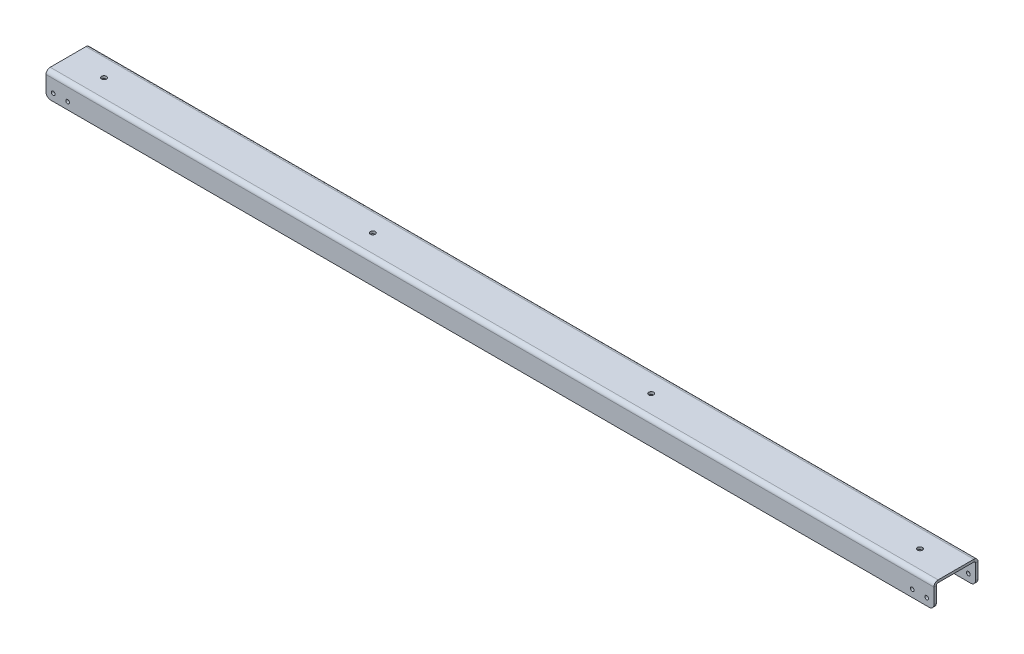
SolidWorks part; units mm, degrees
note: The reader was unsure of these and kept them because the rebuilt part matched: flange length of "Edge-Flange1".
material "6061 Alloy"
ref_plane "Front Plane" through (0, 0, 0) normal (0, 0, 1) x (1, 0, 0)
ref_plane "Top Plane" through (0, 0, 0) normal (0, 1, 0) x (1, 0, 0)
ref_plane "Right Plane" through (0, 0, 0) normal (1, 0, 0) x (0, 0, -1)
sketch "Sketch1" plane through (0, 0, 0) normal (0, 1, 0) x (1, 0, 0)
  line L1 (-587.375, -25.908) -> (587.375, -25.908)
  line L2 (-587.375, -25.908) -> (-587.375, 25.908)
  line L3 (-587.375, 25.908) -> (587.375, 25.908)
  line L4 (587.375, -25.908) -> (587.375, 25.908)
  line L5 (-587.375, -25.908) -> (587.375, 25.908) construction
  line L6 (-587.375, 25.908) -> (587.375, -25.908) construction
  point P0 (0, 0)
  dimension "D1" = 1174.75
  dimension "D2" = 51.816
base flange "Base-Flange1" sketch "Sketch1" thickness 3.2639 reverse thickness direction no parameters "D1"=2.286
edge flange "Edge-Flange1" sketch "Sketch10" flange profiles "Sketch10", "Sketch11" flange angle 90 flange length 28.575 flange position material outside bend radius 2.286 thickness 3.2639 relief rectangular parameters "D1"=3.302, "D6"=10, "D8"=1
sketch "Sketch10" plane through (0, -3.2639, 25.908) normal (0, 0, -1) x (1, 0, 0)
  line L2 (-587.375, 0) -> (-587.375, 28.575)
  line L3 (-587.375, 28.575) -> (587.375, 28.575)
  line L4 (587.375, 28.575) -> (587.375, 0)
  line L9 (587.375, 0) -> (-587.375, 0) construction
  line L10 (587.375, 0) -> (-587.375, 0)
  dimension "D1" = 28.575
sketch "Sketch11" plane through (0, -3.2639, -25.908) normal (0, 0, 1) x (-1, 0, 0)
  line L2 (-587.375, 0) -> (-587.375, 28.575)
  line L3 (-587.375, 28.575) -> (587.375, 28.575)
  line L4 (587.375, 28.575) -> (587.375, 0)
  line L13 (587.375, 0) -> (-587.375, 0) construction
  line L14 (587.375, 0) -> (-587.375, 0)
bend "EdgeBend1" bend radius 2.286 bend angle 90 parameters "D5"=1
bend "EdgeBend2" bend radius 2.286 bend angle 90 parameters "D5"=2
sketch "Sketch12" plane through (0, 0, 29.1719) normal (0, 0, 1) x (1, 0, 0)
  line L0 (587.375, -31.8389) -> (-587.375, -31.8389) construction
  line L1 (555.625, -31.8389) -> (-555.625, -31.8389)
  line L2 (555.625, -31.8389) -> (555.625, 1.4986)
  line L3 (555.625, 1.4986) -> (-555.625, 1.4986)
  line L4 (-555.625, -31.8389) -> (-555.625, 1.4986)
  line L5 (0, 1.4986) -> (0, -31.8389) construction
  line L6 (555.625, -15.1702) -> (-555.625, -15.1702) construction
  line L7 (-587.375, -31.8389) -> (-587.375, -5.5499) construction
  line L8 (587.375, -5.5499) -> (587.375, -31.8389) construction
  point P68 (0, -15.1702)
  dimension "D1" = 31.75
  dimension "D2" = 31.75
  dimension "D3" = 33.3375
extrude "Cut-Extrude1" [suppressed] cut sketch "Sketch12" against normal through all both and the other way through all
hole_wizard "#10 (0.1935) Diameter Hole1" [suppressed] positions "Sketch13" profile "Sketch14" hole size "#10" standard "ANSI Inch"
sketch "Sketch13" [suppressed] plane through (0, 0, 24.5187) normal (0, 0, 1) x (1, 0, 0)
  line L0 (-571.5, -30.075) -> (-571.5, -3) construction
  line L1 (-555.625, -30.075) -> (-587.375, -30.075) construction
  line L2 (587.375, -3) -> (555.625, -3) construction
  line L4 (-555.625, -22.1375) -> (-587.375, -22.1375) construction
  line L5 (-587.375, -30.075) -> (-587.375, -3) construction
  line L7 (-587.375, -22.1375) -> (-587.375, -30.075) construction
  line L9 (-587.375, -26.1063) -> (-577.85, -39.6) construction
  line L11 (-571.5, -30.075) -> (-587.375, -30.075) construction
  line L13 (-579.4375, -30.075) -> (-579.4375, -22.1375) construction
  line L15 (571.5, -30.075) -> (571.5, -3) construction
  line L16 (587.375, -30.075) -> (555.625, -30.075) construction
  line L18 (577.85, -39.6) -> (587.375, -39.6) construction
  line L20 (587.375, -3) -> (587.375, -30.075) construction
  line L22 (571.5, -30.075) -> (587.375, -30.075) construction
  line L24 (579.4375, -30.075) -> (579.4375, -3) construction
  point P0 (563.5625, -20.55)
  point P2 (579.4375, -20.55)
  point P4 (-579.4375, -20.55)
  point P6 (-563.5625, -20.55)
  dimension "D1" = 9.525
  dimension "D2" = 9.525
  dimension "D3" = 7.9375
  dimension "D5" = 9.525
  dimension "D6" = 7.9375
sketch "Sketch14" plane through (563.5625, -20.55, 24.5187) normal (1, 0, 0) x (0, -1, 0)
  line L0 (0, 0) -> (0, 49.0375)
  line L1 (0, 49.0375) -> (2.4574, 49.0375)
  line L2 (2.4574, 49.0375) -> (2.4574, 0)
  line L5 (2.4574, 0) -> (0, 0)
  line L11 (0, -6.35) -> (0, 107.95) construction
  dimension "Thru Hole Dia." = 4.9149
  dimension "Thru Hole Depth" = 49.0375
hole_wizard "#10 (0.1935) Diameter Hole2" positions "Sketch19" profile "Sketch20" hole size "#10" standard "ANSI Inch" end condition through all
sketch "Sketch19" plane through (0, 0, 29.1719) normal (0, 0, 1) x (1, 0, 0)
  line L0 (587.375, -5.5499) -> (587.375, -31.8389) construction
  line L1 (587.375, -31.8389) -> (-587.375, -31.8389) construction
  line L2 (0, -31.8389) -> (0, -5.5499) construction
  line L3 (587.375, -5.5499) -> (-587.375, -5.5499) construction
  point P0 (577.85, -22.3139)
  point P2 (558.8, -22.3139)
  point P16 (-558.8, -22.3139)
  point P17 (-577.85, -22.3139)
  dimension "D1" = 9.525
  dimension "D2" = 19.05
  dimension "D3" = 9.525
sketch "Sketch20" plane through (577.85, -22.3139, 29.1719) normal (1, 0, 0) x (0, -1, 0)
  line L0 (0, 0) -> (0, 58.3438)
  line L1 (0, 58.3438) -> (2.4574, 58.3438)
  line L2 (2.4574, 58.3438) -> (2.4574, 0)
  line L5 (2.4574, 0) -> (0, 0)
  line L11 (0, -6.35) -> (0, 107.95) construction
  dimension "Thru Hole Dia." = 4.9149
  dimension "Thru Hole Depth" = 58.3438
fillet "Fillet2" radius 6.35 4 edges at (-587.375, -31.8389, 27.54) (-587.375, -31.8389, -27.54) (587.375, -31.8389, 27.54) (587.375, -31.8389, -27.54)
hole_wizard "1/4 Clearance Hole1" positions "Sketch23" profile "Sketch22" hole size "1/4" standard "ANSI Inch" end condition through all
sketch "Sketch23" plane through (0, 0, 0) normal (0, 1, 0) x (1, 0, 0)
  line L0 (-587.375, 23.622) -> (-587.375, -23.622) construction
  line L2 (-587.375, 0) -> (587.375, 0) construction
  line L3 (587.375, -23.622) -> (587.375, 23.622) construction
  line L4 (0, -23.622) -> (0, 23.622) construction
  line L5 (-587.375, -23.622) -> (587.375, -23.622) construction
  line L6 (587.375, 23.622) -> (-587.375, 23.622) construction
  point P0 (539.75, 0)
  point P2 (184.15, 0)
  point P6 (-184.15, 0)
  point P8 (-539.75, 0)
  dimension "D1" = 47.625
  dimension "D2" = 47.625
  dimension "D3" = 355.6
sketch "Sketch22" plane through (539.75, 0, 0) normal (1, 0, 0) x (0, 0, 1)
  line L0 (0, 0) -> (0, 31.8389)
  line L1 (0, 31.8389) -> (3.2639, 31.8389)
  line L2 (3.2639, 31.8389) -> (3.2639, 0)
  line L5 (3.2639, 0) -> (0, 0)
  line L11 (0, -6.35) -> (0, 107.95) construction
  dimension "Thru Hole Dia." = 6.5278
  dimension "Thru Hole Depth" = 31.8389
sketch "Bend-Lines1" [suppressed] plane through (0, 0, 0) normal (0, 1, 0) x (1, 0, 0)
sketch "Bounding-Box1" [suppressed] plane through (0, 0, 0) normal (0, 1, 0) x (1, 0, 0)
sheet metal parameters "Sheet-Metal1" thickness 3.2639 parameters "D1"=1.5
flat pattern "Flat-Pattern1" [suppressed]
sketch "Bend-Lines2" plane through (0, 0, 0) normal (0, 1, 0) x (1, 0, 0)
sketch3d "Bounding-Box2" [suppressed]
  line L0 (-609.6, 23.0188, 0) -> (609.6, 23.0188, 0) construction
  line L1 (-609.6, -23.0187, 0) -> (609.6, -23.0187, 0) construction
  line L2 (-609.6, 23.0188, 0) -> (-609.6, -23.0187, 0) construction
  line L3 (609.6, 23.0188, 0) -> (609.6, -23.0187, 0) construction
sheet metal parameters "Sheet-Metal2" thickness 3.2639 parameters "D1"=1.5
flat pattern "Flat-Pattern1"
sketch "Bend-Lines2" plane through (0, 0, 0) normal (0, 1, 0) x (1, 0, 0)
  line L0 (587.375, 24.3388) -> (-587.375, 24.3388) construction
  line L1 (-587.375, -24.3388) -> (587.375, -24.3388) construction
  line L2 (587.375, 24.3388) -> (-587.375, 24.3388) construction
  line L3 (-587.375, -24.3388) -> (587.375, -24.3388) construction
sketch3d "Bounding-Box2" [suppressed]
  line L0 (587.375, 52.6464, 0) -> (-587.375, 52.6464, 0) construction
  line L1 (587.375, -52.6464, 0) -> (-587.375, -52.6464, 0) construction
  line L2 (587.375, 52.6464, 0) -> (587.375, -52.6464, 0) construction
  line L3 (-587.375, 52.6464, 0) -> (-587.375, -52.6464, 0) construction
bend of the flat pattern "Flatten-<EdgeBend1>1"
bend of the flat pattern "Flatten-<EdgeBend2>1"
sheet metal parameters "Sheet-Metal3" thickness 3.2639 parameters "D1"=1.5
flat pattern "Flat-Pattern1"
sketch "Bend-Lines2" plane through (0, 0, 0) normal (0, 1, 0) x (1, 0, 0)
  line L0 (609.6, 23.2859) -> (-609.6, 23.2859) construction
  line L1 (-609.6, -23.2859) -> (609.6, -23.2859) construction
  line L2 (609.6, 23.2859) -> (-609.6, 23.2859) construction
  line L3 (-609.6, -23.2859) -> (609.6, -23.2859) construction
sketch3d "Bounding-Box2" [suppressed]
  line L0 (609.6, 68.003, 0) -> (-609.6, 68.003, 0) construction
  line L1 (609.6, -68.003, 0) -> (-609.6, -68.003, 0) construction
  line L2 (609.6, 68.003, 0) -> (609.6, -68.003, 0) construction
  line L3 (-609.6, 68.003, 0) -> (-609.6, -68.003, 0) construction
bend of the flat pattern "Flatten-<EdgeBend1>1"
bend of the flat pattern "Flatten-<EdgeBend2>1"
sheet metal parameters "Sheet-Metal4" thickness 3.2639 parameters "D1"=1.5
flat pattern "Flat-Pattern5"
sketch "Bend-Lines3" plane through (0, 0, 0) normal (0, 1, 0) x (1, 0, 0)
  line L0 (-555.625, 23.2859) -> (-587.375, 23.2859) construction
  line L1 (-587.375, -23.2859) -> (-555.625, -23.2859) construction
  line L2 (-555.625, 23.2859) -> (-587.375, 23.2859) construction
  line L3 (-587.375, -23.2859) -> (-555.625, -23.2859) construction
sketch3d "Bounding-Box3" [suppressed]
  line L0 (-587.375, -52.128, 0) -> (-587.375, 52.128, 0) construction
  line L1 (-555.625, -52.128, 0) -> (-555.625, 52.128, 0) construction
  line L2 (-587.375, -52.128, 0) -> (-555.625, -52.128, 0) construction
  line L3 (-587.375, 52.128, 0) -> (-555.625, 52.128, 0) construction
bend of the flat pattern "Flatten-<EdgeBend1>1"
bend of the flat pattern "Flatten-<EdgeBend2>1"
sheet metal parameters "Sheet-Metal5" thickness 3.2639 parameters "D1"=1.5
flat pattern "Flat-Pattern5" [suppressed]
sketch "Bend-Lines3" plane through (0, 0, 0) normal (0, 1, 0) x (1, 0, 0)
sketch "Bounding-Box3" [suppressed] plane through (0, 0, 0) normal (0, 1, 0) x (1, 0, 0)
bend of the flat pattern "Flatten-<EdgeBend2>2"
bend of the flat pattern "Flatten-<EdgeBend1>2"
sheet metal parameters "Sheet-Metal6" thickness 3.2639 parameters "D1"=1.5
flat pattern "Flat-Pattern6" [suppressed]
sketch "Bend-Lines4" plane through (0, 0, 0) normal (0, 1, 0) x (1, 0, 0)
sketch "Bounding-Box4" [suppressed] plane through (0, 0, 0) normal (0, 1, 0) x (1, 0, 0)
bend of the flat pattern "Flatten-<EdgeBend2>3"
bend of the flat pattern "Flatten-<EdgeBend1>3"
sheet metal parameters "Sheet-Metal7" thickness 3.2639 parameters "D1"=1.5
flat pattern "Flat-Pattern6" [suppressed]
sketch "Bend-Lines4" plane through (0, 0, 0) normal (0, 1, 0) x (1, 0, 0)
sketch "Bounding-Box4" [suppressed] plane through (0, 0, 0) normal (0, 1, 0) x (1, 0, 0)
bend of the flat pattern "Flatten-<EdgeBend2>3"
bend of the flat pattern "Flatten-<EdgeBend1>3"
sheet metal parameters "Sheet-Metal8" thickness 3.2639 parameters "D1"=1.5
flat pattern "Flat-Pattern1"
sketch "Bend-Lines2" plane through (0, 0, 0) normal (0, 1, 0) x (1, 0, 0)
  line L0 (587.375, 24.3388) -> (-587.375, 24.3388) construction
  line L1 (-587.375, -24.3388) -> (587.375, -24.3388) construction
  line L2 (587.375, 24.3388) -> (-587.375, 24.3388) construction
  line L3 (-587.375, -24.3388) -> (587.375, -24.3388) construction
sketch3d "Bounding-Box2" [suppressed]
  line L0 (-587.375, 52.6461, 0) -> (587.375, 52.6464, 0) construction
  line L1 (-587.375, -52.6464, 0) -> (587.375, -52.6461, 0) construction
  line L2 (-587.375, 52.6461, 0) -> (-587.375, -52.6464, 0) construction
  line L3 (587.375, 52.6464, 0) -> (587.375, -52.6461, 0) construction
bend of the flat pattern "Flatten-<EdgeBend1>1"
bend of the flat pattern "Flatten-<EdgeBend2>1"
sheet metal parameters "Sheet-Metal9" thickness 3.2639 parameters "D1"=1.5
flat pattern "Flat-Pattern1"
sketch "Bend-Lines2" plane through (0, 0, 0) normal (0, 1, 0) x (1, 0, 0)
  line L0 (587.375, 26.5557) -> (-587.375, 26.5557) construction
  line L1 (-587.375, -26.5557) -> (587.375, -26.5557) construction
  line L2 (587.375, 26.5557) -> (-587.375, 26.5557) construction
  line L3 (-587.375, -26.5557) -> (587.375, -26.5557) construction
sketch3d "Bounding-Box2" [suppressed]
  line L0 (-587.375, 55.7781, 0) -> (587.375, 55.7784, 0) construction
  line L1 (-587.375, -55.7784, 0) -> (587.375, -55.7781, 0) construction
  line L2 (-587.375, 55.7781, 0) -> (-587.375, -55.7784, 0) construction
  line L3 (587.375, 55.7784, 0) -> (587.375, -55.7781, 0) construction
bend of the flat pattern "Flatten-<EdgeBend1>1"
bend of the flat pattern "Flatten-<EdgeBend2>1"
